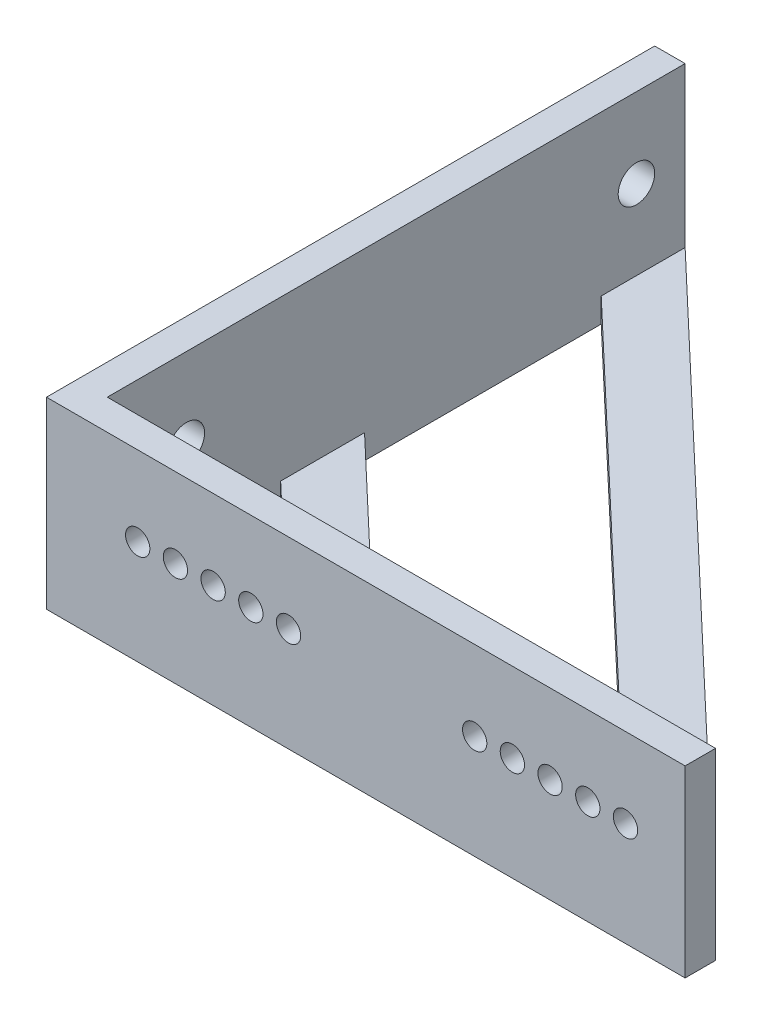
SolidWorks part; units mm, degrees
ref_plane "Front Plane" through (0, 0, 0) normal (0, 0, 1) x (1, 0, 0)
ref_plane "Top Plane" through (0, 0, 0) normal (0, 1, 0) x (1, 0, 0)
ref_plane "Right Plane" through (0, 0, 0) normal (1, 0, 0) x (0, 0, -1)
sketch "Sketch1" plane through (0, 0, 0) normal (1, 0, 0) x (0, 0, -1)
  line L1 (0, 0) -> (50, 0)
  line L2 (0, 0) -> (0, 15.1)
  line L3 (0, 15.1) -> (50, 15.1)
  line L4 (50, 0) -> (50, 15.1)
  dimension "D1" = 50
  dimension "D2" = 15.1
extrude "Boss-Extrude1" add sketch "Sketch1" along normal blind 2.5
sketch "Sketch3" plane through (2.5, 0, 0) normal (1, 0, 0) x (0, 0, -1)
  line L0 (0, 8.55) -> (50, 8.55) construction
  line L2 (50, 0) -> (50, 15.1) construction
  line L3 (50, 15.1) -> (0, 15.1) construction
  circle A0 centre (46, 8.55) radius 1.5
  circle A1 centre (9, 8.55) radius 1.5
  dimension "D1" = 37
  dimension "D2" = 4
  dimension "D3" = 3
  dimension "D4" = 6.55
extrude "Cut-Extrude1" cut sketch "Sketch3" against normal through all
sketch "Sketch4" plane through (2.5, 0, 0) normal (1, 0, 0) x (0, 0, -1)
  line L0 (50, 15.1) -> (0, 15.1) construction
  line L1 (0, 0) -> (2.5, 0)
  line L2 (0, 0) -> (0, 15.1)
  line L3 (0, 15.1) -> (2.5, 15.1)
  line L4 (2.5, 0) -> (2.5, 15.1)
  dimension "D1" = 2.5
extrude "Boss-Extrude2" add sketch "Sketch4" along normal blind 50
sketch "Sketch6" plane through (0, 0, -2.5) normal (0, 0, -1) x (-1, 0, 0)
  line L0 (-2.5, 8.55) -> (-52.5, 8.55) construction
  line L1 (-2.5, 0) -> (-2.5, 15.1) construction
  line L3 (-52.5, 15.1) -> (-2.5, 15.1) construction
  circle A0 centre (-7.5, 8.55) radius 1
  circle A1 centre (-10.6, 8.55) radius 1
  circle A2 centre (-13.7, 8.55) radius 1
  circle A3 centre (-16.8, 8.55) radius 1
  circle A4 centre (-19.9, 8.55) radius 1
  circle A5 centre (-35.2, 8.55) radius 1
  circle A6 centre (-38.3, 8.55) radius 1
  circle A7 centre (-41.4, 8.55) radius 1
  circle A8 centre (-44.5, 8.55) radius 1
  circle A9 centre (-47.6, 8.55) radius 1
  dimension "D1" = 2
  dimension "D2" = 5
  dimension "D4" = 15.3
  dimension "D6" = 6.55
  dimension "D3" = 5
  dimension "D5" = 5
extrude "Cut-Extrude2" cut sketch "Sketch6" against normal blind 45
sketch "Sketch8" plane through (2.5, 0, 0) normal (1, 0, 0) x (0, 0, -1)
  line L0 (2.5, 0) -> (2.5, 15.1) construction
  line L1 (2.5, 2) -> (50, 2)
  line L2 (2.5, 2) -> (2.5, 0)
  line L3 (2.5, 0) -> (50, 0)
  line L4 (50, 2) -> (50, 0)
  dimension "D1" = 2
extrude "Boss-Extrude3" add sketch "Sketch8" along normal up to surface (50 mm away) up to face at (52.5, 7.55, -1.25)
sketch "Sketch9" plane through (0, 2, 0) normal (0, 1, 0) x (1, 0, 0)
  line L0 (45.2405, 2.5) -> (2.5, 43.1034)
  line L1 (52.5, 2.5) -> (2.5, 2.5) construction
  line L2 (2.5, 50) -> (2.5, 2.5) construction
  line L3 (52.5, 2.5) -> (2.5, 50)
  line L4 (17.5, 2.5) -> (2.5, 16.75)
  line L5 (2.5, 43.1034) -> (2.5, 23.6466)
  line L6 (2.5, 23.6466) -> (24.7595, 2.5)
  line L7 (24.7595, 2.5) -> (45.2405, 2.5)
  line L8 (17.5, 2.5) -> (2.5, 2.5)
  line L9 (2.5, 2.5) -> (2.5, 16.75)
  line L10 (52.5, 2.5) -> (52.5, 50)
  line L11 (52.5, 2.5) -> (52.5, 50) construction
  line L12 (52.5, 50) -> (2.5, 50) construction
  line L13 (52.5, 50) -> (2.5, 50)
  dimension "D1" = 5
  dimension "D2" = 5
  dimension "D3" = 15
extrude "Cut-Extrude3" cut sketch "Sketch9" against normal through all
